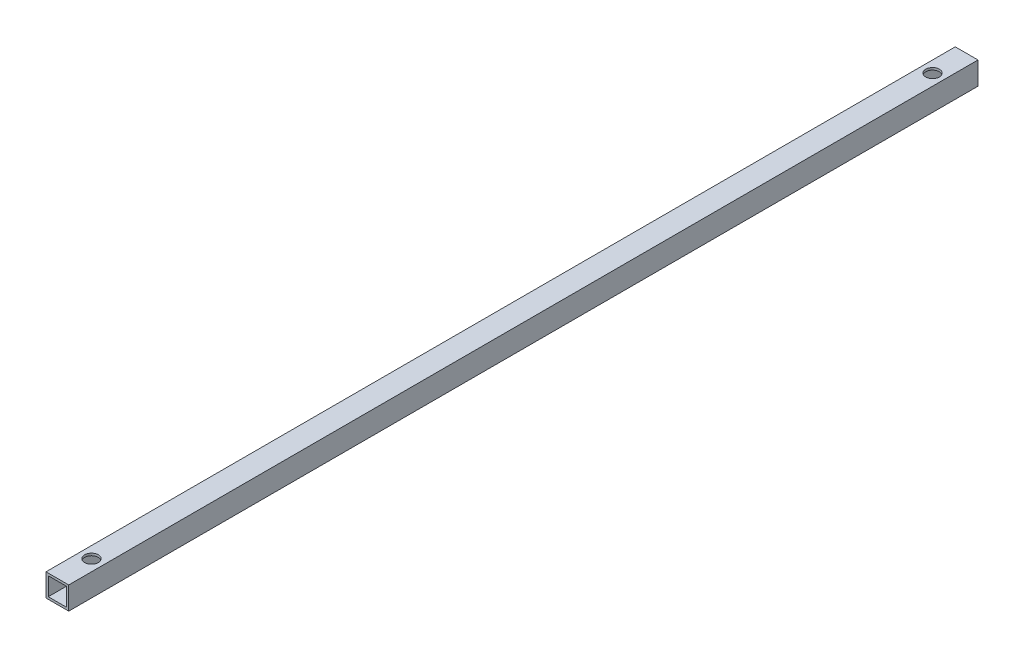
SolidWorks part; units mm, degrees
material "5052-H34"
ref_plane "正面" through (0, 0, 0) normal (0, 0, 1) x (1, 0, 0)
ref_plane "平面" through (0, 0, 0) normal (0, 1, 0) x (1, 0, 0)
ref_plane "右側面" through (0, 0, 0) normal (1, 0, 0) x (0, 0, -1)
sketch "ｽｹｯﾁ1" plane through (0, 0, 0) normal (0, 0, 1) x (1, 0, 0)
  line L1 (-5, 5) -> (5, 5)
  line L2 (-5, 5) -> (-5, -5)
  line L3 (-5, -5) -> (5, -5)
  line L4 (5, 5) -> (5, -5)
  line L5 (-5, 5) -> (5, -5) construction
  line L6 (-5, -5) -> (5, 5) construction
  point P0 (0, 0)
  dimension "D1" = 10
  dimension "D2" = 10
extrude "押し出し-薄板1" add sketch "ｽｹｯﾁ1" along normal blind 400 thin thin type one direction reverse wall 1
sketch "ｽｹｯﾁ2" plane through (0, 5, 0) normal (0, 1, 0) x (1, 0, 0)
  line L0 (-5, -200) -> (5, -200) construction
  line L1 (-5, -400) -> (-5, 0) construction
  line L2 (5, -400) -> (5, 0) construction
  line L3 (0, -400) -> (0, -385) construction
  line L4 (5, -400) -> (-5, -400) construction
  circle A0 centre (0, -385) radius 1.6
  circle A1 centre (0, -15) radius 1.6
  dimension "D1" = 3.2
  dimension "D2" = 15
extrude "ｶｯﾄ - 押し出し1" cut sketch "ｽｹｯﾁ2" against normal through all
sketch "ｽｹｯﾁ3" plane through (0, 5, 0) normal (0, 1, 0) x (1, 0, 0)
  circle A0 centre (0, -385) radius 3
  circle A1 centre (0, -385) radius 1.6 construction
  circle A2 centre (0, -15) radius 3
  dimension "D1" = 6
extrude "ｶｯﾄ - 押し出し2" cut sketch "ｽｹｯﾁ3" against normal blind 1
